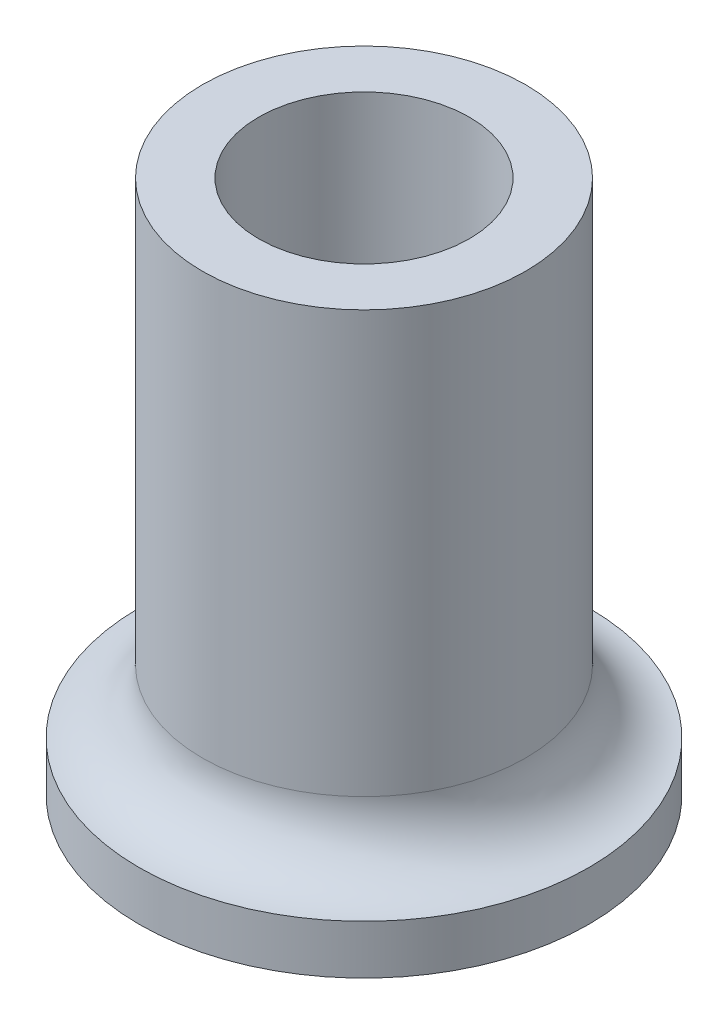
SolidWorks part; units mm, degrees
ref_plane "前基準面" through (0, 0, 0) normal (0, 0, 1) x (1, 0, 0)
ref_plane "上基準面" through (0, 0, 0) normal (0, 1, 0) x (1, 0, 0)
ref_plane "右基準面" through (0, 0, 0) normal (1, 0, 0) x (0, 0, -1)
sketch "草圖1" plane through (0, 0, 0) normal (0, 1, 0) x (1, 0, 0)
  circle A0 centre (0, 0) radius 16
  circle A1 centre (0, 0) radius 7.5
  dimension "D1" = 32
  dimension "D2" = 15
extrude "填料-伸長1" add sketch "草圖1" along normal blind 3.5
sketch "草圖2" plane through (0, 3.5, 0) normal (0, 1, 0) x (1, 0, 0)
  circle A0 centre (0, 0) radius 11.5
  circle A1 centre (0, 0) radius 7.5 construction
  circle A2 centre (0, 0) radius 7.5
  dimension "D1" = 23
extrude "填料-伸長2" add sketch "草圖2" along normal blind 34.5
fillet "圓角3" radius 4.5 1 edges at (0, 3.5, 11.5)
